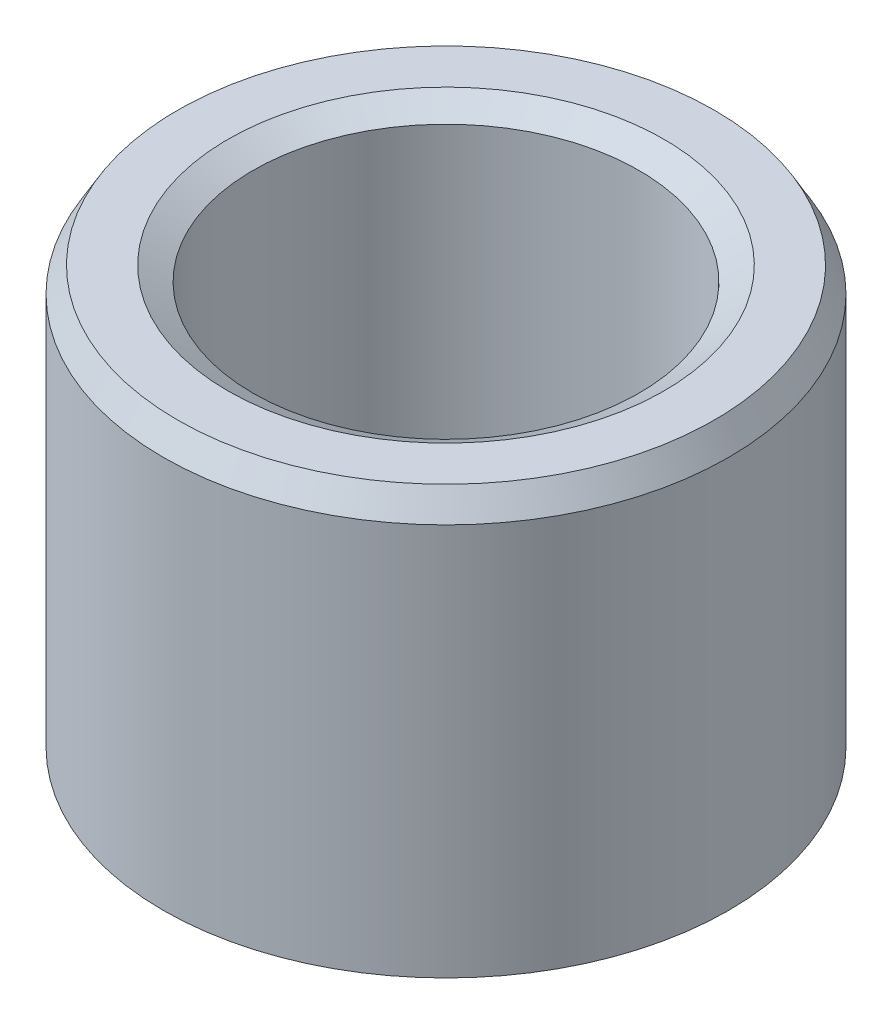
SolidWorks part; units mm, degrees
ref_plane "Front Plane" through (0, 0, 0) normal (0, 0, 1) x (1, 0, 0)
ref_plane "Top Plane" through (0, 0, 0) normal (0, 1, 0) x (1, 0, 0)
ref_plane "Right Plane" through (0, 0, 0) normal (1, 0, 0) x (0, 0, -1)
sketch "Sketch1" plane through (0, 0, 0) normal (0, 1, 0) x (1, 0, 0)
  circle A0 centre (0, 0) radius 27.5
  dimension "SLEEVE_OD" = 55
extrude "Boss-Extrude1" add sketch "Sketch1" along normal blind 41.9849
sketch "Sketch2" plane through (0, 0, 0) normal (0, 1, 0) x (1, 0, 0)
  circle A0 centre (0, 0) radius 18.7657
  dimension "BORE_D" = 37.5314
extrude "Cut-Extrude1" cut sketch "Sketch2" along normal through all
chamfer "Chamfer1" distance 2.4318 angle 30 4 edges at (0, 41.9849, 18.7657) (0, 0, 18.7657) (0, 0, 27.5) (0, 41.9849, 27.5) first distance on face at (0, 41.9849, 18.7657) first distance on face at (0, 0, 18.7657) first distance on face at (0, 41.9849, 27.5)
